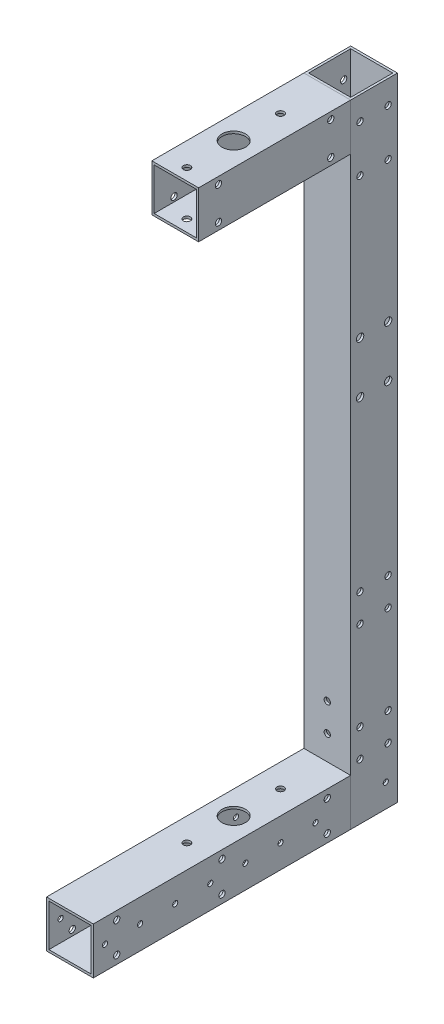
SolidWorks part; units mm, degrees
note: '?' marks a value the reader was unsure of.
material "6061 合金"
ref_plane "前视基准面" through (0, 0, 0) normal (0, 0, 1) x (1, 0, 0)
ref_plane "上视基准面" through (0, 0, 0) normal (0, 1, 0) x (1, 0, 0)
ref_plane "右视基准面" through (0, 0, 0) normal (1, 0, 0) x (0, 0, -1)
sketch3d "3D草图1"
  line L0 (0, 0, 0) -> (0, 260, 0)
  line L1 (0, 260, 0) -> (0, 260, 75)
  line L3 (0, 10, 0) -> (0, 10, 120)
  dimension "D1" = 10
  dimension "D8" = 75
  dimension "D2" = 260
  dimension "D3" = 120
  dimension "D6" = 0
other "方形管 25 X 10 X 1(1)"
ref_plane "基准面1" through (0, 0, 0) normal (0, 1, 0) x (1, 0, 0)
sketch "Sketch1" plane through (0, 0, 0) normal (0, 1, 0) x (1, 0, 0)
  line L0 (-9, -9) -> (-9, 9)
  line L1 (10, -10) -> (-10, -10)
  line L2 (10, -10) -> (10, 10)
  line L3 (10, 10) -> (-10, 10)
  line L4 (-10, -10) -> (-10, 10)
  line L5 (0, 10) -> (0, -10) construction
  line L6 (10, 0) -> (-10, 0) construction
  line L7 (9, 9) -> (-9, 9)
  line L8 (9, -9) -> (9, 9)
  line L9 (9, -9) -> (-9, -9)
  point P0 (0, 0)
  point P4 (0, 0)
  point P33 (0, 0)
  dimension "D1" = 20
  dimension "D2" = 1
  dimension "D3" = 20
ref_axis "基准轴1" through (0, 0, 0) along (0, 1, 0)?
other "方形管 20 X 20 X 2(3)"
ref_plane "基准面3" through (0, 10, 0) normal (0, 0, 1) x (1, 0, 0)
sketch "Sketch12" plane through (0, 10, 0) normal (0, 0, 1) x (1, 0, 0)
  line L0 (-9, 9) -> (9, 9)
  line L1 (-10, -10) -> (10, -10)
  line L2 (-10, -10) -> (-10, 10)
  line L3 (-10, 10) -> (10, 10)
  line L4 (10, -10) -> (10, 10)
  line L5 (0, 10) -> (0, -10) construction
  line L6 (-10, 0) -> (10, 0) construction
  line L7 (9, -9) -> (9, 9)
  line L8 (-9, -9) -> (9, -9)
  line L9 (-9, -9) -> (-9, 9)
  line L10 (10, 10) -> (10, -260) construction
  point P0 (0, 0)
  point P4 (0, 0)
  point P33 (0, 0)
  dimension "D1" = 20
  dimension "D2" = 1
other "剪裁/延伸2"
sketch "草图4" plane through (0, 250, 0) normal (0, -1, 0) x (1, 0, 0)
  line L0 (0, 120) -> (0, 10) construction
  line L1 (10, 75) -> (-10, 75) construction
  line L6 (-10, 10) -> (10, 10) construction
  line L7 (-10, 120) -> (10, 120) construction
  circle A0 centre (0, 70) radius 1.5
  circle A1 centre (0, 30) radius 1.5
  dimension "D2" = 3
  dimension "D1" = 40
  dimension "D3" = 5
extrude "切除-拉伸1" cut sketch "草图4" against normal up to next and the other way up to surface
sketch "草图5" plane through (0, 250, 0) normal (0, -1, 0) x (1, 0, 0)
  line L0 (0, 30) -> (0, 70) construction
  circle A0 centre (0, 50) radius 5
  dimension "D1" = 10
extrude "切除-拉伸2" cut sketch "草图5" against normal up to next and the other way up to surface
sketch "草图6" plane through (0, 270, 0) normal (0, 1, 0) x (1, 0, 0)
  line L0 (0, -50) -> (0, -75) construction
  line L1 (10, -75) -> (-10, -75) construction
  line L2 (0, -50) -> (10, -50) construction
  line L3 (10, -75) -> (10, -10) construction
  circle A16 centre (0, -30) radius 1.5 construction
  circle A17 centre (0, -30) radius 1.5
  circle A18 centre (0, -50) radius 5
  circle A19 centre (0, -70) radius 1.5
  dimension "D1" = 10
  dimension "D2" = 25
extrude "切除-拉伸3" cut sketch "草图6" against normal up to next (1 mm away)
sketch "草图9" plane through (-10, 0, 0) normal (-1, 0, 0) x (0, 0, 1)
  line L0 (42.5, 260) -> (75, 260) construction
  line L1 (42.5, 270) -> (42.5, 250) construction
  line L2 (75, 250) -> (10, 250) construction
  line L3 (75, 270) -> (75, 250) construction
  line L4 (75, 270) -> (10, 270) construction
  line L5 (0, 270) -> (0, 0) construction
  line L6 (-10, 270) -> (10, 270) construction
  line L7 (0, 250) -> (-10, 250) construction
  line L8 (120, 20) -> (120, 0) construction
  line L9 (120, 10) -> (-10, 10) construction
  line L10 (-10, 270) -> (-10, 0) construction
  line L11 (65, 20) -> (65, 0) construction
  line L12 (120, 20) -> (10, 20) construction
  line L13 (120, 0) -> (10, 0) construction
  line L14 (-10, 30) -> (10, 30) construction
  line L15 (10, 270) -> (10, 0) construction
  line L16 (-10, 80) -> (10, 80) construction
  circle A0 centre (-6, 74) radius 1.35
  circle A1 centre (-6, 240) radius 1.35
  circle A5 centre (-6, 86) radius 1.35
  circle A7 centre (6, 86) radius 1.35
  circle A9 centre (6, 74) radius 1.35
  circle A15 centre (6, 240) radius 1.35
  circle A22 centre (115, 10) radius 1.1
  circle A23 centre (100, 10) radius 1.1
  circle A26 centre (85, 10) radius 1.1
  circle A27 centre (70, 10) radius 1.1
  circle A36 centre (-6, 36) radius 1.35
  circle A38 centre (6, 36) radius 1.35
  circle A40 centre (-6, 24) radius 1.35
  circle A42 centre (6, -4) radius 1.35
  circle A44 centre (-6, -4) radius 1.35
  circle A45 centre (6, -16) radius 1.35
  circle A46 centre (-6, -16) radius 1.35
  circle A50 centre (6, 24) radius 1.35
  circle A86 centre (55, 10) radius 1.1
  circle A87 centre (40, 10) radius 1.1
  circle A88 centre (25, 10) radius 1.1
  circle A90 centre (-5, 10) radius 1.1
  circle A91 centre (20, 16.5) radius 1.35
  circle A92 centre (20, 3.5) radius 1.35
  circle A95 centre (-6, 260) radius 1.35
  circle A99 centre (6, 260) radius 1.35
  circle A100 centre (18.5, 267) radius 1.35
  circle A108 centre (66.5, 267) radius 1.35
  circle A109 centre (66.5, 253) radius 1.35
  circle A110 centre (18.5, 253) radius 1.35
  circle A111 centre (10, 10) radius 1.1 [skipped]
  circle A112 centre (110, 3.5) radius 1.35
  circle A113 centre (110, 16.5) radius 1.35
  circle A114 centre (65, 16.5) radius 1.35
  circle A115 centre (65, 3.5) radius 1.35
  dimension "D3" = 2.7
  dimension "D7" = 9
  dimension "D9" = 2.2
  dimension "D15" = 10
  dimension "D1" = 48
  dimension "D2" = 14
  dimension "D4" = 20
  dimension "D5" = 20
  dimension "D6" = 12
  dimension "D8" = 5
  dimension "D10" = 15
  dimension "D11" = 13
  dimension "D12" = 90
  dimension "D13" = 12
  dimension "D14" = 12
  dimension "D16" = 10
  dimension "D17" = 12
  dimension "D18" = 70
extrude "切除-拉伸6" cut sketch "草图9" against normal through all
sketch "草图12" plane through (0, 0, -10) normal (0, 0, -1) x (-1, 0, 0)
  line L0 (0, 46.5) -> (0, 26.5) construction
  line L1 (-10, 270) -> (-10, 0) construction
  line L2 (10, 270) -> (10, 0) construction
  line L3 (-10, 26.5) -> (10, 26.5) construction
  line L4 (-10, 26.5) -> (-10, 46.5) construction
  line L5 (-10, 20) -> (-10, 0)
  line L6 (10, 20) -> (-10, 20)
  line L7 (10, 0) -> (10, 20)
  line L8 (-10, 0) -> (10, 0)
  line L9 (-10, 20) -> (-10, 0) construction
  line L10 (10, 20) -> (-10, 20) construction
  line L11 (10, 0) -> (10, 20) construction
  line L12 (-10, 0) -> (10, 0) construction
  line L13 (-10, 46.5) -> (10, 46.5) construction
  line L14 (10, 26.5) -> (10, 46.5) construction
  line L15 (0, 36.5) -> (10, 36.5) construction
  circle A0 centre (0, 42.5) radius 1.35
  circle A1 centre (0, 30.5) radius 1.35
  dimension "D5" = 2.7
  dimension "D1" = 0
  dimension "D2" = 6.5
  dimension "D3" = 20
  dimension "D4" = 12
extrude "切除-拉伸7" cut sketch "草图12" against normal through all
sketch "草图13" plane through (0, 0, -10) normal (0, 0, -1) x (-1, 0, 0)
  line L0 (10, 270) -> (10, 0) construction
  line L1 (-10, 270) -> (10, 270)
  line L2 (-10, 270) -> (-10, -30)
  line L3 (-10, -30) -> (10, -30)
  line L4 (10, 270) -> (10, -30)
  circle A0 centre (0, 30.5) radius 1.35 construction
  circle A1 centre (0, 42.5) radius 1.35 construction
  circle A2 centre (0, 30.5) radius 1.35
  circle A3 centre (0, 42.5) radius 1.35
  dimension "D1" = 300
extrude "凸台-拉伸2" [suppressed] add sketch "草图13" along normal blind 1 separate body
ref_plane "基准面4" [suppressed] through (-10, 174.1421, -11) normal (0, 1, 0) x (1, 0, 0)
sketch "草图15" plane through (10, 0, 0) normal (1, 0, 0) x (0, 0, -1)
  line L0 (0, 270) -> (0, 0) construction
  line L1 (-10, 270) -> (10, 270) construction
  circle A0 centre (-6, 180) radius 1.6
  circle A1 centre (-6, 158) radius 1.6
  circle A2 centre (6, 158) radius 1.6
  circle A3 centre (6, 180) radius 1.6
  dimension "D1" = 3.2
  dimension "D2" = 22
  dimension "D3" = 12
  dimension "D4" = 90
extrude "切除-拉伸8" cut sketch "草图15" against normal through all
move or copy body "实体-移动/复制1" [suppressed] bodies to move or copy 158 159 160 161
sketch "草图10" [suppressed] plane through (10, 0, 0) normal (1, 0, 0) x (0, 0, -1)
  line L0 (10, 480) -> (10, 0) construction
  line L1 (-10, 0) -> (10, 0)
  line L2 (-10, 0) -> (-10, 40)
  line L3 (-10, 40) -> (10, 40)
  line L4 (10, 0) -> (10, 40)
  line L5 (-115.8579, 40) -> (-144.1421, 40)
  line L9 (-10, 174.1421) -> (-184.1421, 0)
  line L10 (-184.1421, 0) -> (-155.8579, 0)
  line L11 (-155.8579, 0) -> (-10, 145.8579)
  line L12 (-10, 145.8579) -> (-10, 174.1421)
  line L13 (-144.1421, 40) -> (-184.1421, 0)
  line L14 (-184.1421, 0) -> (-155.8579, 0)
  line L15 (-155.8579, 0) -> (-115.8579, 40)
  circle A0 centre (-6.5, 10) radius 1.35 construction
  circle A1 centre (6.5, 10) radius 1.35 construction
  circle A2 centre (6.5, 30) radius 1.35 construction
  circle A3 centre (-6.5, 30) radius 1.35 construction
  circle A4 centre (-6.5, 10) radius 1.35
  circle A5 centre (6.5, 10) radius 1.35
  circle A6 centre (6.5, 30) radius 1.35
  circle A7 centre (-6.5, 30) radius 1.35
  circle A8 centre (-174.3112, 4.8812) radius 1.35 construction
  circle A9 centre (-155.9264, 4.8812) radius 1.35 construction
  circle A10 centre (-132.5919, 28.2157) radius 1.35 construction
  circle A11 centre (-150.9767, 28.2157) radius 1.35 construction
  circle A12 centre (-174.3112, 4.8812) radius 1.35
  circle A13 centre (-155.9264, 4.8812) radius 1.35
  circle A14 centre (-132.5919, 28.2157) radius 1.35
  circle A15 centre (-150.9767, 28.2157) radius 1.35
  dimension "D1" = 40
  dimension "D2" = 0
extrude "凸台-拉伸1" [suppressed] add sketch "草图10" along normal blind 5 separate body
